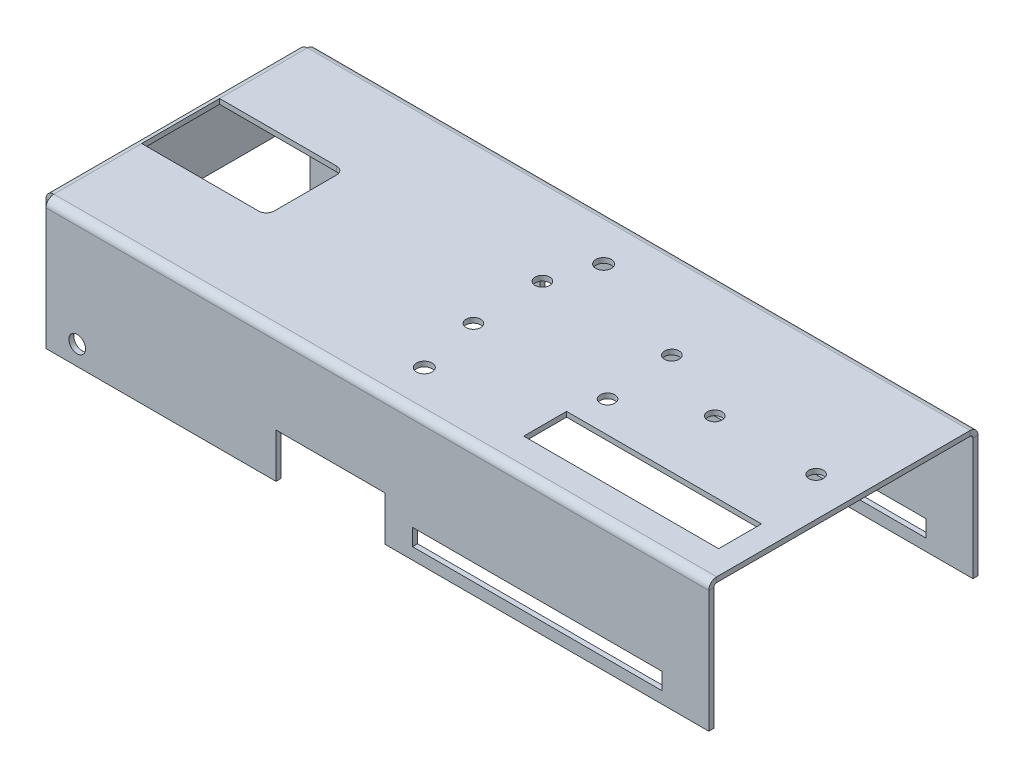
SolidWorks part; units mm, degrees
note: The reader was unsure of these and kept them because the rebuilt part matched: flange length of "Edge-Flange1", "Edge-Flange3", "Edge-Flange7".
ref_plane "Front Plane" through (0, 0, 0) normal (0, 0, 1) x (1, 0, 0)
ref_plane "Top Plane" through (0, 0, 0) normal (0, 1, 0) x (1, 0, 0)
ref_plane "Right Plane" through (0, 0, 0) normal (1, 0, 0) x (0, 0, -1)
sketch "Sketch1" plane through (0, 0, 0) normal (0, 1, 0) x (1, 0, 0)
  line L1 (0, 0) -> (170, 0)
  line L2 (0, 0) -> (0, 65)
  line L3 (0, 65) -> (170, 65)
  line L4 (170, 0) -> (170, 65)
  dimension "D2" = 170
  dimension "D1" = 65
sheet metal parameters "Sheet-Metal1" thickness 1.29 parameters "D1"=0.7366
base flange "Base-Flange1" sketch "Sketch1" thickness 1.29 reverse thickness direction no parameters "D1"=0.7366
edge flange "Edge-Flange1" sketch "Sketch6" flange angle 90 flange length 32 flange position bend outside bend radius 0.7366 thickness 1.29 relief rectangular parameters "D6"=10
sketch "Sketch6" plane through (0, -1.29, 0) normal (0, 0, 1) x (-1, 0, 0)
  line L1 (0, 0) -> (-170, 0) construction
  line L2 (0, 0) -> (-170, 0)
  line L3 (-170, 0) -> (-170, 32)
  line L4 (-170, 32) -> (0, 32)
  line L5 (0, 32) -> (0, 0)
bend "EdgeBend1" bend radius 0.7366 bend angle 90 parameters "D5"=1
edge flange "Edge-Flange3" sketch "Sketch12" flange angle 90 flange length 15 flange position bend outside bend radius 0.7366 thickness 1.29 relief rectangular parameters "D6"=10
sketch "Sketch12" plane through (0, -1.29, 0) normal (-1, 0, 0) x (0, 0, -1)
  line L0 (65, 0) -> (0, 0) construction
  line L1 (65, 0) -> (0, 0)
  line L2 (0, 0) -> (0, 15)
  line L3 (0, 15) -> (65, 15)
  line L4 (65, 15) -> (65, 0)
bend "EdgeBend3" bend radius 0.7366 bend angle 90 parameters "D5"=3
sketch "Sketch16" plane through (0, 0, 0) normal (0, 1, 0) x (1, 0, 0)
  line L1 (164, 17.5) -> (114, 17.5)
  line L2 (11.3797, 32.5) -> (66.0765, 32.5) construction
  line L3 (114, 6.5) -> (164, 6.5)
  line L4 (164, 17.5) -> (164, 6.5)
  line L5 (13, 32.5) -> (13, 50032.5) construction
  line L6 (170, 65) -> (0, 65) construction
  line L7 (114, 17.5) -> (114, 6.5)
  line L8 (30, 42.5) -> (0, 42.5)
  line L9 (0, 65) -> (0, 0) construction
  line L10 (30, 22.5) -> (0, 22.5)
  line L11 (32, 24.5) -> (32, 40.5)
  line L12 (0, 42.5) -> (0, 22.5)
  line L13 (170, 0) -> (170, 65) construction
  line L14 (0, 0) -> (170, 0) construction
  arc A3 (32, 40.5) -> (30, 42.5) centre (30, 40.5) ccw
  arc A4 (32, 24.5) -> (30, 22.5) centre (30, 24.5) cw
  circle A5 centre (86, 9) radius 2
  circle A6 centre (86, 55) radius 2
  dimension "D1" = 32.5
  dimension "D3" = 9
  dimension "D5" = 26
  dimension "D4" = 15
  dimension "D6" = 50
  dimension "D7" = 138
  dimension "D9" = 8
  dimension "D10" = 28
  dimension "D11" = 46
extrude "Cut-Extrude1" cut sketch "Sketch16" against normal up to next normal cut yes
edge flange "Edge-Flange7" sketch "Sketch32" flange angle 90 flange length 32 flange position bend outside bend radius 0.7366 thickness 1.29 relief rectangular parameters "D6"=10
sketch "Sketch32" plane through (0, -1.29, -65) normal (0, 0, -1) x (1, 0, 0)
  line L0 (170, 0) -> (0, 0) construction
  line L1 (170, 0) -> (0, 0)
  line L2 (0, 0) -> (0, 32)
  line L3 (0, 32) -> (170, 32)
  line L4 (170, 32) -> (170, 0)
bend "EdgeBend7" bend radius 0.7366 bend angle 90 parameters "D5"=8
sketch "Sketch34" plane through (0, 0, -67.0266) normal (0, 0, -1) x (-1, 0, 0)
  line L15 (-158, -30.29) -> (-94, -25.99) construction
  line L16 (-158, -25.99) -> (-94, -30.29) construction
  line L17 (-87, -33.29) -> (-87, -21.88)
  line L18 (-59, -21.88) -> (-87, -21.88)
  line L19 (-59, -33.29) -> (-59, -21.88)
  line L20 (-59, -33.29) -> (-87, -33.29)
  line L21 (-94, -25.99) -> (-94, -30.29)
  line L22 (-158, -30.29) -> (-94, -30.29)
  line L23 (-158, -25.99) -> (-158, -30.29)
  line L24 (-158, -25.99) -> (-94, -25.99)
  circle A1 centre (-8, -28.29) radius 2.15
  point P31 (-126, -28.14)
extrude "Cut-Extrude5" cut sketch "Sketch34" against normal through all normal cut yes
sketch "Sketch36" plane through (0, 0, 0) normal (0, 1, 0) x (1, 0, 0)
  circle A0 centre (116.5, 25.5) radius 1.875
  circle A1 centre (115, 43.5) radius 1.875
  circle A3 centre (82.5, 25.1) radius 1.875
  circle A4 centre (82, 43.3) radius 1.875
  dimension "D5" = 3.75
  dimension "D6" = 3.75
  dimension "D7" = 3.75
  dimension "D8" = 3.75
  dimension "D9" = 34
  dimension "D10" = 0.4
  dimension "D11" = 33
  dimension "D12" = 0.2
extrude "Cut-Extrude6" cut sketch "Sketch36" against normal blind 10 normal cut yes
sketch "Sketch37" plane through (0, 0, 0) normal (0, 1, 0) x (1, 0, 0)
  line L1 (170, 0) -> (170, 65) construction
  circle A0 centre (160, 35.5) radius 1.875
  circle A2 centre (134, 35.5) radius 1.875
  dimension "D1" = 3.75
  dimension "D2" = 10
  dimension "D3" = 3.75
  dimension "D4" = 36
extrude "Cut-Extrude7" cut sketch "Sketch37" against normal blind 10 normal cut yes
flat pattern "Flat-Pattern1" [suppressed]
sketch "Bend-Lines1" plane through (0, 0, 0) normal (0, 1, 0) x (1, 0, 0)
  line L0 (170, 66.0851) -> (0, 66.0851) construction
  line L1 (-1.0851, 65) -> (-1.0851, 0) construction
  line L2 (170, 66.0851) -> (0, 66.0851) construction
  line L3 (0, -1.0851) -> (170, -1.0851) construction
  line L5 (-1.0851, 65) -> (-1.0851, 0) construction
  line L7 (0, -1.0851) -> (170, -1.0851) construction
  point P0 (171.0851, 0)
  point P1 (171.0851, 65)
  point P8 (-2.1702, 64.0585)
  point P9 (-16.4336, 64.0585)
  point P10 (-16.4336, 0.9415)
  point P11 (-2.1702, 0.9415)
sketch3d "Bounding-Box1" [suppressed]
  line L0 (170, 98.4336, 0) -> (-16.4336, 98.4336, 0) construction
  line L1 (170, -33.4336, 0) -> (-16.4336, -33.4336, 0) construction
  line L2 (170, 98.4336, 0) -> (170, -33.4336, 0) construction
  line L3 (-16.4336, 98.4336, 0) -> (-16.4336, -33.4336, 0) construction
bend of the flat pattern "Flatten-<EdgeBend1>1"
bend of the flat pattern "Flatten-<EdgeBend3>1"
bend of the flat pattern "Flatten-<EdgeBend7>1"
sketch "Sketch39" [suppressed] plane through (0, 0, 0) normal (0, 1, 0) x (1, 0, 0)
  line L0 (170, 66.0851) -> (0, 66.0851) construction
  line L1 (25, 67.1702) -> (0, 67.1702)
  line L2 (25, 67.1702) -> (25, 65)
  line L3 (25, 65) -> (0, 65)
  line L4 (0, 67.1702) -> (0, 65)
  line L5 (25, 67.1702) -> (0, 65) construction
  line L6 (25, 65) -> (0, 67.1702) construction
  line L7 (170, 98.4336) -> (170, -33.4336) construction
  line L8 (170, 67.1702) -> (145, 67.1702)
  line L9 (170, 67.1702) -> (170, 65)
  line L10 (170, 65) -> (145, 65)
  line L11 (145, 67.1702) -> (145, 65)
  line L12 (170, 67.1702) -> (145, 65) construction
  line L13 (170, 65) -> (145, 67.1702) construction
  line L14 (-34.5139, 32.0867) -> (182.8962, 32.0867) construction
  line L15 (50, 67.1702) -> (75, 67.1702)
  line L16 (50, 67.1702) -> (50, 65)
  line L17 (50, 65) -> (75, 65)
  line L18 (75, 67.1702) -> (75, 65)
  line L19 (50, 67.1702) -> (75, 65) construction
  line L20 (50, 65) -> (75, 67.1702) construction
  line L21 (95, 67.1702) -> (120, 67.1702)
  line L22 (95, 67.1702) -> (95, 65)
  line L23 (95, 65) -> (120, 65)
  line L24 (120, 67.1702) -> (120, 65)
  line L25 (95, 67.1702) -> (120, 65) construction
  line L26 (95, 65) -> (120, 67.1702) construction
  line L27 (95, -0.8266) -> (120, -2.9968) construction
  line L28 (95, -2.9968) -> (120, -0.8266) construction
  line L29 (50, -0.8266) -> (75, -2.9968) construction
  line L30 (50, -2.9968) -> (75, -0.8266) construction
  line L31 (170, -0.8266) -> (145, -2.9968) construction
  line L32 (170, -2.9968) -> (145, -0.8266) construction
  line L33 (25, -0.8266) -> (0, -2.9968) construction
  line L34 (25, -2.9968) -> (0, -0.8266) construction
  line L35 (120, -2.9968) -> (120, -0.8266)
  line L36 (95, -0.8266) -> (120, -0.8266)
  line L37 (95, -2.9968) -> (95, -0.8266)
  line L38 (95, -2.9968) -> (120, -2.9968)
  line L39 (75, -2.9968) -> (75, -0.8266)
  line L40 (50, -0.8266) -> (75, -0.8266)
  line L41 (50, -2.9968) -> (50, -0.8266)
  line L42 (50, -2.9968) -> (75, -2.9968)
  line L43 (145, -2.9968) -> (145, -0.8266)
  line L44 (170, -0.8266) -> (145, -0.8266)
  line L45 (170, -2.9968) -> (170, -0.8266)
  line L46 (170, -2.9968) -> (145, -2.9968)
  line L47 (0, -2.9968) -> (0, -0.8266)
  line L48 (25, -0.8266) -> (0, -0.8266)
  line L49 (25, -2.9968) -> (25, -0.8266)
  line L50 (25, -2.9968) -> (0, -2.9968)
  point P0 (12.5, 66.0851)
  point P8 (157.5, 66.0851)
  point P15 (62.5, 66.0851)
  point P20 (107.5, 66.0851)
  point P43 (107.5, -1.9117)
  point P44 (62.5, -1.9117)
  point P45 (157.5, -1.9117)
  point P46 (12.5, -1.9117)
  dimension "D1" = 25
  dimension "D2" = 25
  dimension "D3" = 0
  dimension "D4" = 25
  dimension "D5" = 25
  dimension "D6" = 25
  dimension "D7" = 25
extrude "Cut-Extrude8" [suppressed] cut sketch "Sketch39" against normal blind 10
sketch "Sketch40" [suppressed] plane through (0, 0, 0) normal (0, 1, 0) x (1, 0, 0)
  line L0 (-1.0851, 65) -> (-1.0851, 0) construction
  line L1 (-2.1702, 55) -> (0, 55)
  line L2 (-2.1702, 55) -> (-2.1702, 65)
  line L3 (-2.1702, 65) -> (0, 65)
  line L4 (0, 55) -> (0, 65)
  line L5 (-2.1702, 55) -> (0, 65) construction
  line L6 (-2.1702, 65) -> (0, 55) construction
  line L7 (-16.4336, 65) -> (25, 65) construction
  line L8 (-41.4412, 32.5) -> (193.1059, 32.5) construction
  line L9 (-2.1702, 0) -> (0, 10) construction
  line L10 (-2.1702, 10) -> (0, 0) construction
  line L11 (0, 10) -> (0, 0)
  line L12 (-2.1702, 0) -> (0, 0)
  line L13 (-2.1702, 10) -> (-2.1702, 0)
  line L14 (-2.1702, 10) -> (0, 10)
  point P0 (-1.0851, 60)
  point P15 (-1.0851, 5)
  dimension "D1" = 10
extrude "Cut-Extrude9" [suppressed] cut sketch "Sketch40" against normal blind 10
